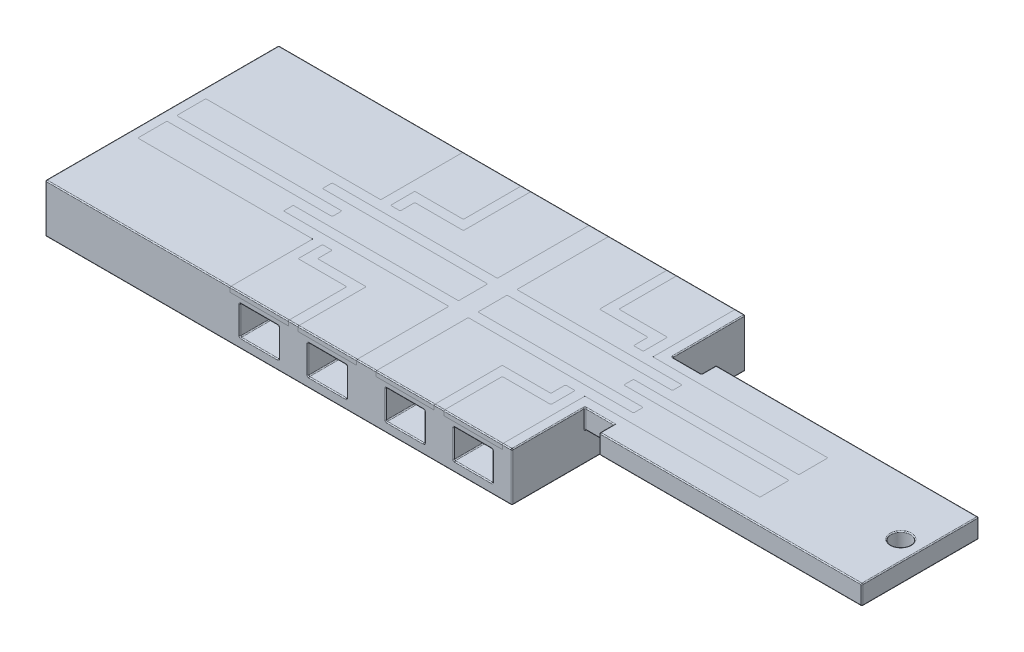
SolidWorks part; units mm, degrees
other "mid_str_4T_sensing_elem"
other "mid_str_4T_sensing"
ref_plane "Front Plane" through (0, 0, 0) normal (0, 0, 1) x (1, 0, 0)
ref_plane "Top Plane" through (0, 0, 0) normal (0, 1, 0) x (1, 0, 0)
ref_plane "Right Plane" through (0, 0, 0) normal (1, 0, 0) x (0, 0, -1)
sketch "Sketch: Beam Surfaces" plane through (0, 0, 0) normal (0, 1, 0) x (1, 0, 0)
  line L35 (45, -6) -> (18, -6)
  line L36 (45, -6) -> (45, 6)
  line L37 (45, 6) -> (18, 6)
  line L38 (18, 6) -> (18, 4.5)
  line L39 (18, 4.5) -> (15, 4.5)
  line L40 (15, 4.5) -> (15, 12)
  line L41 (15, 12) -> (-33, 12)
  line L42 (-33, 12) -> (-33, -12)
  line L44 (-33, -12) -> (15, -12)
  line L45 (15, -12) -> (15, -4.5)
  line L46 (15, -4.5) -> (18, -4.5)
  line L47 (18, -4.5) -> (18, -6)
  line L73 (33, -6) -> (33, 6)
extrude "Beam Surfaces" add sketch "Sketch: Beam Surfaces" against normal blind 2 separate body contours L35 L73 L37 L38 L39 L40 L41 L42 L44 L45 L46 L47 | L73 L35 L36 L37 region at (39, 0, 0) region at (-3.9238, 0, 0)
sketch "Sketch: Ball Bearing Holder" [suppressed] plane through (0, -2, 0) normal (0, -1, 0) x (1, 0, 0)
  line L1 (33, -6) -> (45, -6)
  line L2 (33, -6) -> (33, 6)
  line L3 (33, 6) -> (45, 6)
  line L4 (45, -6) -> (45, 6)
  line L5 (45, 6) -> (45, -6) construction
extrude "Mount" [suppressed] add sketch "Sketch: Ball Bearing Holder" along normal blind 4
sketch "Sketch: Ball Bearing Hole" [suppressed] plane through (0, -6, 0) normal (0, -1, 0) x (1, 0, 0)
  line L0 (39, 4) -> (39, -4) construction
  circle A0 centre (39, 0) radius 4
  point P4 (39, 0)
revolve "Hole" [suppressed] cut sketch "Sketch: Ball Bearing Hole" angle 180 about L0
sketch "Sketch: Ball Bearing" [suppressed] plane through (0, -6, 0) normal (0, -1, 0) x (1, 0, 0)
  line L0 (39, 4) -> (39, -4) construction
  circle A0 centre (39, 0) radius 4
  point P4 (39, 0)
revolve "Metal Ball" [suppressed] add sketch "Sketch: Ball Bearing" angle 360 about L0
sketch "Sketch: Ball Bearing Hole Rim" [suppressed] plane through (0, -6, 0) normal (0, -1, 0) x (1, 0, 0)
  circle A0 centre (39, 0) radius 3.8
  circle M1 centre (39, 0) radius 4
  line M2 (33, 6) -> (33, -6)
  line M3 (33, -6) -> (45, -6)
  line M4 (45, -6) -> (45, 6)
  line M5 (45, 6) -> (33, 6)
extrude "Hole Rim" [suppressed] add sketch "Sketch: Ball Bearing Hole Rim" along normal blind 0.2 contours M5 M2 M3 M4 M1
fillet "Mount Fillets" [suppressed] radius 0.1
sketch "Sketch: Free End Hole" plane through (0, 0, 0) normal (0, 1, 0) x (1, 0, 0)
  circle A1 centre (43, 0) radius 1
extrude "Free End Hole" cut sketch "Sketch: Free End Hole" against normal up to surface (2 mm away) up to face at (13, -2, 0)
fillet "Free End Hole Fillets" radius 0.1 2 edges at (43, -2, 1) (43, 0, 1)
sketch "Sketch: Cantilever Base" plane through (0, -2, 0) normal (0, -1, 0) x (1, 0, 0)
  line L0 (-33, -12) -> (-33, 12) construction
  line L1 (-33, -12) -> (15, -12)
  line L2 (-33, -12) -> (-33, 12)
  line L3 (-33, 12) -> (15, 12)
  line L4 (15, -12) -> (15, 12)
extrude "Cantilever Base" add sketch "Sketch: Cantilever Base" along normal blind 3
fillet "Cantilever Fillets" radius 0.1 35 edges at (15, -2, 0) (16.5, -2, -4.5) (18, -2, -5.25) (18, -2, 5.25) (-33, 0, 0) (-9, 0, -12) (18, -1, -4.5) (15, -1, -4.5) (18, -1, -6) (31.5, -2, -6) (45, -1, -6) (45, -2, 0) (45, -1, 6) (31.5, -2, 6) (18, -1, 6) (15, -1, 4.5) (16.5, -2, 4.5) (15, 0, -8.25) (16.5, 0, -4.5) (18, 0, -5.25) (31.5, 0, -6) (45, 0, 0) (31.5, 0, 6) (18, 0, 5.25) (16.5, 0, 4.5) (15, 0, 8.25) (-9, 0, 12) (-33, -2.5, 12) (-33, -2.5, -12) (15, -2.5, 12) (15, -2.5, -12) (15, -5, 0) (-9, -5, -12) (-33, -5, 0) (-9, -5, 12)
sketch "Sketch: Conductive Traces" plane through (0, 0, 0) normal (0, 1, 0) x (1, 0, 0)
  line L21 (18, -2.5) -> (1, -2.5)
  line L24 (14, -12) -> (14, -3.5)
  line L25 (14, -3.5) -> (32, -3.5)
  line L27 (32, 3.5) -> (14, 3.5)
  line L28 (14, 3.5) -> (14, 12)
  line L31 (1, 2.5) -> (18, 2.5)
  line L33 (13, -3.5) -> (13, -6)
  line L35 (45, -6) -> (18, -6) construction
  line L36 (45, -6) -> (45, 6) construction
  line L37 (45, 6) -> (18, 6) construction
  line L38 (18, 6) -> (18, 4.5) construction
  line L39 (18, 4.5) -> (15, 4.5) construction
  line L40 (15, 4.5) -> (15, 12) construction
  line L41 (15, 12) -> (0, 12) construction
  line L44 (0, -12) -> (15, -12) construction
  line L45 (15, -12) -> (15, -4.5) construction
  line L46 (15, -4.5) -> (18, -4.5) construction
  line L47 (18, -4.5) -> (18, -6) construction
  line L48 (13, 3.5) -> (13, 6)
  line L49 (8, -12) -> (8, -6)
  line L50 (8, -6) -> (13, -6)
  line L51 (18, -2.5) -> (18, -1.5)
  line L52 (18, -1.5) -> (1, -1.5)
  line L53 (1, -1.5) -> (1, 1.5)
  line L54 (1, 1.5) -> (18, 1.5)
  line L55 (18, 1.5) -> (18, 2.5)
  line L56 (32, -3.5) -> (32, -0.5)
  line L57 (32, -0.5) -> (15, -0.5)
  line L58 (15, -0.5) -> (15, 0.5)
  line L59 (15, 0.5) -> (32, 0.5)
  line L60 (32, 0.5) -> (32, 3.5)
  line L61 (13, 6) -> (8, 6)
  line L62 (8, 6) -> (8, 12)
  line L63 (1, -2.5) -> (1, -12)
  line L64 (1, 2.5) -> (1, 12)
  line L65 (13, -3.5) -> (12, -3.5)
  line L66 (12, -3.5) -> (12, -5)
  line L67 (12, -5) -> (7, -5)
  line L68 (7, -5) -> (7, -12)
  line L69 (13, 3.5) -> (12, 3.5)
  line L70 (12, 3.5) -> (12, 5)
  line L71 (12, 5) -> (7, 5)
  line L72 (7, 5) -> (7, 12)
  line L73 (33, -6) -> (33, 6) construction
  line L74 (0, 12) -> (0, -12) construction
  line L75 (1, -12) -> (7, -12)
  line L76 (8, -12) -> (14, -12)
  line L77 (1, 12) -> (7, 12)
  line L78 (8, 12) -> (14, 12)
extrude "Space for Conductive Traces" cut sketch "Sketch: Conductive Traces" against normal blind 0.5
fillet "Space for Conductive Traces Fillets" radius 0.1 28 edges at (7, -0.25, 5) (12, -0.25, 5) (12, -0.25, 3.5) (13, -0.25, 3.5) (13, -0.25, 6) (8, -0.25, 6) (14, -0.25, 3.5) (32, -0.25, 3.5) (32, -0.25, 0.5) (32, -0.25, -0.5) (32, -0.25, -3.5) (14, -0.25, -3.5) (8, -0.25, -6) (13, -0.25, -6) (13, -0.25, -3.5) (12, -0.25, -3.5) (12, -0.25, -5) (7, -0.25, -5) (1, -0.25, -2.5) (18, -0.25, -2.5) (18, -0.25, -1.5) (1, -0.25, -1.5) (1, -0.25, 1.5) (18, -0.25, 1.5) (18, -0.25, 2.5) (1, -0.25, 2.5) (15, -0.25, -0.5) (15, -0.25, 0.5)
mirror "Space for mid_str_4T_sensing_elem Reference" about plane through (0, 0, 0) normal (1, 0, 0) of "Space for Conductive Traces", "Space for Conductive Traces Fillets"
extrude "Conductive Traces" add sketch "Conductive Traces Sketch<5>" against normal blind 0.5 separate body
sketch "Conductive Traces Sketch<5>" plane through (0, 0, 0) normal (0, 1, 0) x (1, 0, 0) same geometry as "Sketch: Conductive Traces"
fillet "Conductive Traces Fillets" radius 0.1 26 edges at (12, -0.25, -3.5) (12, -0.25, 3.5) (15, -0.25, 0.5) (32, -0.25, 3.5) (32, -0.25, 0.5) (32, -0.25, -0.5) (32, -0.25, -3.5) (15, -0.25, -0.5) (18, -0.25, -2.5) (18, -0.25, 1.5) (18, -0.25, -1.5) (18, -0.25, 2.5) (7, -0.25, 5) (7, -0.25, -5) (12, -0.25, -5) (13, -0.25, 6) (13, -0.25, -3.5) (12, -0.25, 5) (13, -0.25, 3.5) (13, -0.25, -6) (8, -0.25, -6) (1, -0.25, -2.5) (8, -0.25, 6) (1, -0.25, -1.5) (1, -0.25, 1.5) (1, -0.25, 2.5)
fillet "Electrical Contacts Fillets" radius 0.1 4 edges at (11, 0, -12) (4, 0, -12) (11, 0, 12) (4, 0, 12)
mirror "mid_str_4T_sensing_elem Reference" about plane through (0, 0, 0) normal (1, 0, 0) of bodies 117
sketch "Sketch0" plane through (0, 0, 0) normal (0, 1, 0) x (1, 0, 0)
  line L1 (2, 12) -> (6, 12)
  line L2 (2, 12) -> (2, 7)
  line L3 (2, 7) -> (6, 7)
  line L4 (6, 12) -> (6, 7)
  line L6 (9, 12) -> (13, 12)
  line L7 (9, 12) -> (9, 7)
  line L8 (9, 7) -> (13, 7)
  line L9 (13, 12) -> (13, 7)
  line L10 (9, -7) -> (13, -7)
  line L11 (9, -7) -> (9, -12)
  line L12 (9, -12) -> (13, -12)
  line L13 (13, -7) -> (13, -12)
  line L14 (2, -7) -> (6, -7)
  line L15 (2, -7) -> (2, -12)
  line L16 (2, -12) -> (6, -12)
  line L17 (6, -7) -> (6, -12)
extrude "Cut-Extrude0" cut sketch "Sketch0" against normal blind 3 from offset 1 offset against normal yes
fillet "Fillet0" radius 0.1 48 edges at (6, -2.5, -12) (2, -2.5, -12) (13, -2.5, -12) (9, -2.5, -12) (9, -2.5, 12) (13, -2.5, 12) (2, -2.5, 12) (6, -2.5, 12) (6, -2.5, -7) (2, -2.5, -7) (4, -1, -7) (6, -1, -9.5) (4, -1, -12) (2, -1, -9.5) (13, -2.5, -7) (9, -2.5, -7) (11, -1, -7) (13, -1, -9.5) (11, -1, -12) (9, -1, -9.5) (9, -2.5, 7) (13, -2.5, 7) (2, -2.5, 7) (6, -2.5, 7) (11, -1, 12) (13, -1, 9.5) (11, -1, 7) (9, -1, 9.5) (4, -1, 12) (6, -1, 9.5) (4, -1, 7) (2, -1, 9.5) (4, -4, -7) (11, -4, -7) (11, -4, 7) (4, -4, 7) (11, -4, -12) (4, -4, -12) (4, -4, 12) (11, -4, 12) (13, -4, -9.5) (2, -4, -9.5) (9, -4, -9.5) (6, -4, -9.5) (6, -4, 9.5) (2, -4, 9.5) (9, -4, 9.5) (13, -4, 9.5)
mirror "Mirror0" about plane through (0, 0, 0) normal (1, 0, 0) of "Cut-Extrude0", "Fillet0"
